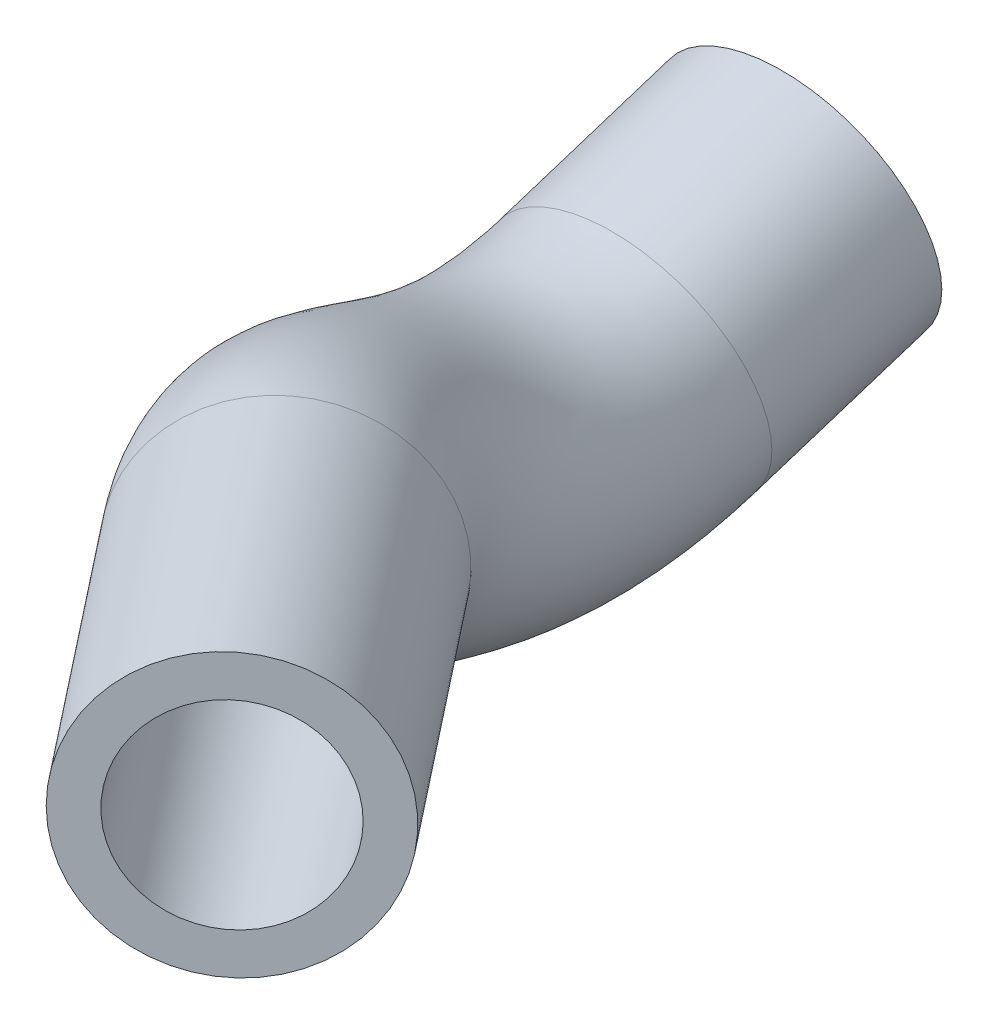
SolidWorks part; units mm, degrees
material "Silicon Rubber"
ref_plane "X-Y Datum" through (0, 0, 0) normal (0, 0, 1) x (1, 0, 0)
ref_plane "X-Z Datum" through (0, 0, 0) normal (0, 1, 0) x (1, 0, 0)
ref_plane "Y-Z Datum" through (0, 0, 0) normal (1, 0, 0) x (0, 0, -1)
sketch3d "3DSketch1"
  line L0 (144.1662, 29.7864, -53.3572) -> (145.2995, 25.3597, -34.8633)
  line L1 (157.1297, 36.7283, 12.1101) -> (181.0722, 40.6983, 41.4802)
  line L2 (157.1297, 36.7283, 12.1101) -> (181.0722, 40.6983, 41.4802) construction
  line L3 (157.6988, 36.8227, 12.8083) -> (181.0722, 40.6983, 41.4802) construction
  line L4 (181.0722, 40.6983, 41.4802) -> (157.1297, 36.7283, 12.1101) construction
  line L5 (144.1662, 29.7864, -53.3572) -> (144.9217, 26.8353, -41.028) construction
  circle A0 centre (144.9217, 26.8353, -41.028) radius 8.2804 construction
  circle A1 centre (144.1662, 29.7864, -53.3572) radius 9.525 construction
  circle A4 centre (144.9217, 26.8353, -41.028) radius 8.2804 construction
  circle A10 centre (181.0722, 40.6983, 41.4802) radius 10.2862 construction
  circle A11 centre (157.6988, 36.8227, 12.8083) radius 7.366 construction
  circle A12 centre (181.0722, 40.6983, 41.4802) radius 10.2862 construction
  circle A13 centre (157.6988, 36.8227, 12.8083) radius 7.366 construction
  circle A14 centre (144.1662, 29.7864, -53.3572) radius 9.525 construction
  spline S0 degree 3 poles (145.2995, 25.3597, -34.8633) (146.6909, 19.9246, -12.1566) (145.4925, 34.7987, -2.1651) (157.1297, 36.7283, 12.1101) knots 0 0 0 0 1 1 1 1
  point P7 (187.5361, 41.7702, 49.4096)
  point P10 (153.0699, 36.0551, 7.13)
  point P12 (187.5361, 41.7702, 49.4096)
  point P14 (153.0699, 36.0551, 7.13)
  point P16 (145.4143, 24.9111, -32.9893)
  point P20 (144.7329, 27.573, -44.1103)
  point P22 (145.4143, 24.9111, -32.9893)
  point P24 (144.7329, 27.573, -44.1103)
  dimension "D1" = 19.05
  dimension "D2" = 38.1
sweep "Sweep1" add path "3DSketch1" circular profile diameter 26.9875 parameters "D3"=26.9875
sweep "Cut-Sweep1" cut path "3DSketch1<2>" circular profile diameter 19.05 parameters "D3"=19.05
sketch3d "3DSketch1<2>" same geometry as "3DSketch1"
